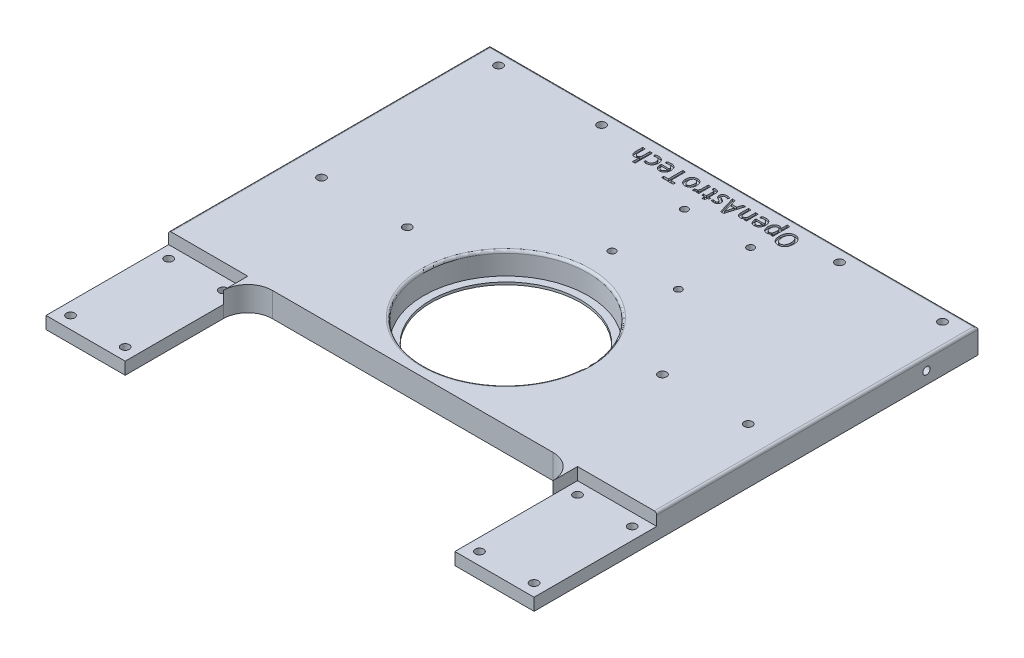
SolidWorks part; units mm, degrees
ref_plane "Ebene vorne" through (0, 0, 0) normal (0, 0, 1) x (1, 0, 0)
ref_plane "Ebene oben" through (0, 0, 0) normal (0, 1, 0) x (1, 0, 0)
ref_plane "Ebene rechts" through (0, 0, 0) normal (1, 0, 0) x (0, 0, -1)
sketch "Skizze1" plane through (0, 0, 0) normal (0, 1, 0) x (1, 0, 0)
  line L1 (-99.5, -210) -> (99.5, -210)
  line L2 (-99.5, -210) -> (-99.5, 210)
  line L3 (-99.5, 210) -> (99.5, 210)
  line L4 (99.5, -210) -> (99.5, 210)
  line L5 (-99.5, -210) -> (99.5, 210) construction
  line L6 (-99.5, 210) -> (99.5, -210) construction
  point P0 (0, 0)
  dimension "D1" = 199
  dimension "D2" = 420
extrude "Aufsatz-Linear austragen1" add sketch "Skizze1" along normal blind 10
ref_plane "Ebene1" through (0, -97.5366, 81.8429) normal (0, -0.766, 0.6428) x (1, 0, 0)
sketch "Skizze2" plane through (0, -97.5366, 81.8429) normal (0, -0.766, 0.6428) x (1, 0, 0)
  line L1 (-99.5, 167.2972) -> (99.5, 167.2972) construction
  circle A0 centre (0, 147.2972) radius 5
  dimension "D1" = 10
  dimension "D2" = 20
extrude "Schnitt-Linear austragen1" [suppressed] cut sketch "Skizze2" against normal blind 30 and the other way blind 10
sketch "Skizze3" [suppressed] plane through (0, -67.9923, 57.0523) normal (0, -0.766, 0.6428) x (1, 0, 0)
  circle A0 centre (0, 101.3345) radius 5
  dimension "D1" = 10
extrude "Aufsatz-Linear austragen2" [suppressed] add sketch "Skizze3" along normal blind 0.1
sketch "Skizze4" plane through (0, -97.5366, 81.8429) normal (0, -0.766, 0.6428) x (1, 0, 0)
  line L0 (0, 167.2972) -> (0, 159.9002) construction
  line L1 (-99.5, 167.2972) -> (99.5, 167.2972) construction
  line L2 (-25, 167.2972) -> (-25, 202.2972)
  line L3 (-25, 202.2972) -> (25, 202.2972)
  line L4 (-25, 167.2972) -> (25, 167.2972)
  line L5 (25, 167.2972) -> (25, 202.2972)
  point P10 (0, 202.2972)
  dimension "D1" = 50
  dimension "D2" = 35
extrude "Aufsatz-Linear austragen3" [suppressed] add sketch "Skizze4" against normal blind 10 separate body
sketch "Skizze5" plane through (0, 10, 0) normal (0, 1, 0) x (1, 0, 0)
  line L0 (0, 0) -> (0, -210) construction
  line L1 (-99.5, -210) -> (99.5, -210) construction
  line L2 (99.5, -210) -> (18, -210)
  line L3 (-18, -210) -> (-99.5, -56)
  line L4 (-99.5, 210) -> (-99.5, -210) construction
  line L5 (-99.5, -56) -> (-99.5, -210)
  line L6 (-99.5, -210) -> (-18, -210)
  line L7 (99.5, -56) -> (99.5, -210)
  line L8 (18, -210) -> (99.5, -56)
  line L9 (-99.5, 210) -> (-99.5, 125)
  line L10 (-99.5, 125) -> (99.5, 125)
  line L11 (99.5, -210) -> (99.5, 210) construction
  line L12 (99.5, 125) -> (99.5, 210)
  line L13 (99.5, 210) -> (-99.5, 210)
  line L14 (67.211, -56) -> (-67.211, -56)
  line L15 (-67.211, -56) -> (-2.6461, -178)
  line L16 (67.211, -56) -> (2.6461, -178)
  line L17 (-2.6461, -178) -> (2.6461, -178)
  line L18 (2.6461, -178) -> (0, -183) construction
  line L19 (-2.6461, -178) -> (0, -183) construction
  point P27 (0, -56)
  dimension "D1" = 36
  dimension "D2" = 154
  dimension "D3" = 85
  dimension "D4" = 32
  dimension "D5" = 27
extrude "Schnitt-Linear austragen2" cut sketch "Skizze5" against normal blind 10
sketch "Skizze6" plane through (0, 10, 0) normal (0, 1, 0) x (1, 0, 0)
  line L0 (0, -210) -> (0, -178) construction
  line L1 (-18, -210) -> (18, -210) construction
  line L2 (-2.6461, -178) -> (2.6461, -178) construction
  line L3 (0, -196.59) -> (-21.075, -196.59) construction
  circle A0 centre (-11, -205) radius 1.7
  circle A1 centre (-11, -188.18) radius 1.7
  circle A2 centre (11, -205) radius 1.7
  circle A3 centre (11, -188.18) radius 1.7
  dimension "D1" = 3.4
  dimension "D2" = 11
  dimension "D3" = 5
  dimension "D4" = 13.41
extrude "Schnitt-Linear austragen3" cut sketch "Skizze6" against normal through all
sketch "Skizze7" plane through (0, 0, 0) normal (0, -1, 0) x (1, 0, 0)
  line L0 (-11, 205) -> (-11, 210) construction
  line L1 (-18, 210) -> (18, 210) construction
  line L2 (-11, 205) -> (-5.1092, 205) construction
  line L3 (-11, 208.4064) -> (-8.05, 206.7032)
  line L4 (-8.05, 206.7032) -> (-8.05, 203.2968)
  line L5 (-11, 201.5936) -> (-8.05, 203.2968)
  line L6 (-11, 201.5936) -> (-13.95, 203.2968)
  line L7 (-13.95, 206.7032) -> (-13.95, 203.2968)
  line L8 (-11, 208.4064) -> (-13.95, 206.7032)
  line L9 (0, 210) -> (0, 121.6034) construction
  line L10 (11, 205) -> (11, 188.18) construction
  line L11 (11, 196.59) -> (0, 196.59) construction
  line L12 (11, 208.4064) -> (8.05, 206.7032)
  line L13 (11, 201.5936) -> (8.05, 203.2968)
  line L14 (8.05, 206.7032) -> (8.05, 203.2968)
  line L15 (11, 201.5936) -> (13.95, 203.2968)
  line L16 (13.95, 206.7032) -> (13.95, 203.2968)
  line L17 (11, 208.4064) -> (13.95, 206.7032)
  line L18 (-8.05, 186.4768) -> (-8.05, 189.8832)
  line L19 (-11, 191.5864) -> (-13.95, 189.8832)
  line L20 (-11, 191.5864) -> (-8.05, 189.8832)
  line L21 (-13.95, 186.4768) -> (-13.95, 189.8832)
  line L22 (-11, 184.7736) -> (-13.95, 186.4768)
  line L23 (-11, 184.7736) -> (-8.05, 186.4768)
  line L24 (8.05, 186.4768) -> (8.05, 189.8832)
  line L25 (11, 191.5864) -> (8.05, 189.8832)
  line L26 (11, 191.5864) -> (13.95, 189.8832)
  line L27 (13.95, 186.4768) -> (13.95, 189.8832)
  line L28 (11, 184.7736) -> (13.95, 186.4768)
  line L29 (11, 184.7736) -> (8.05, 186.4768)
  point P10 (-8.05, 205)
  dimension "D1" = 120
  dimension "D2" = 5.9
extrude "Schnitt-Linear austragen4" cut sketch "Skizze7" against normal blind 4
sketch "Skizze8" plane through (0, 10, 0) normal (0, 1, 0) x (1, 0, 0)
  line L0 (99.5, 115.41) -> (78.872, 115.41) construction
  line L1 (99.5, -56) -> (99.5, 125) construction
  line L2 (-99.5, 125) -> (99.5, 125) construction
  dimension "D1" = 9.59
ref_plane "Ebene2" through (0, 62.6966, -52.6087) normal (0, 0.766, -0.6428) x (-1, 0, 0)
sketch "Skizze9" plane through (0, 62.6966, -52.6087) normal (0, 0.766, -0.6428) x (-1, 0, 0)
  line L0 (-99.5, -81.9813) -> (-78.872, -81.9813) construction
  line L1 (-99.5, 49.3264) -> (-99.5, -89.3277) construction
  line L2 (0, -45.2589) -> (0, -16.2619) construction
  circle A0 centre (-94.5, -81.9813) radius 1.7
  circle A1 centre (94.5, -81.9813) radius 1.7
  circle A2 centre (-30, -81.9813) radius 1.7
  circle A3 centre (30, -81.9813) radius 1.7
  dimension "D1" = 3.4
  dimension "D2" = 5
  dimension "D3" = 30
extrude "Schnitt-Linear austragen5" [suppressed] cut sketch "Skizze9" against normal through all and the other way through all
ref_plane "Ebene3" through (0, 55.0361, -46.1808) normal (0, 0.766, -0.6428) x (-1, 0, 0)
sketch "Skizze10" [suppressed] plane through (0, 55.0361, -46.1808) normal (0, 0.766, -0.6428) x (-1, 0, 0)
  line L0 (-95, -81.9813) -> (-100, -81.9813) construction
  line L1 (-95, -81.9813) -> (-95, -30.0694) construction
  line L2 (-95, -78.7482) -> (-97.8, -80.3647)
  line L3 (-97.8, -80.3647) -> (-97.8, -83.5979)
  line L4 (-95, -85.2145) -> (-97.8, -83.5979)
  line L5 (-95, -85.2145) -> (-92.2, -83.5979)
  line L6 (-92.2, -80.3647) -> (-92.2, -83.5979)
  line L7 (-95, -78.7482) -> (-92.2, -80.3647)
  line L8 (0, 0) -> (0, -45.6283) construction
  line L9 (-30, -81.9813) -> (-95, -81.9813) construction
  line L10 (-62.5, -81.9813) -> (-62.5, -23.1343) construction
  line L11 (-32.8, -80.3647) -> (-32.8, -83.5979)
  line L12 (-30, -85.2145) -> (-32.8, -83.5979)
  line L13 (-30, -85.2145) -> (-27.2, -83.5979)
  line L14 (-27.2, -80.3647) -> (-27.2, -83.5979)
  line L15 (-30, -78.7482) -> (-27.2, -80.3647)
  line L16 (-30, -78.7482) -> (-32.8, -80.3647)
  line L17 (95, -78.7482) -> (92.2, -80.3647)
  line L18 (92.2, -80.3647) -> (92.2, -83.5979)
  line L19 (95, -85.2145) -> (92.2, -83.5979)
  line L20 (95, -85.2145) -> (97.8, -83.5979)
  line L21 (97.8, -80.3647) -> (97.8, -83.5979)
  line L22 (95, -78.7482) -> (97.8, -80.3647)
  line L23 (30, -78.7482) -> (32.8, -80.3647)
  line L24 (30, -78.7482) -> (27.2, -80.3647)
  line L25 (27.2, -80.3647) -> (27.2, -83.5979)
  line L26 (30, -85.2145) -> (27.2, -83.5979)
  line L27 (30, -85.2145) -> (32.8, -83.5979)
  line L28 (32.8, -80.3647) -> (32.8, -83.5979)
  point P9 (-97.8, -81.9813)
  point P31 (97.8, -81.9813)
  dimension "D1" = 120
  dimension "D2" = 5.6
extrude "Schnitt-Linear austragen6" [suppressed] cut sketch "Skizze10" against normal blind 10 and the other way blind 5
sketch "Skizze13" plane through (0, 10, 0) normal (0, 1, 0) x (1, 0, 0)
  line L0 (67.211, -56) -> (99.5, -56) construction
  line L1 (67.211, -56) -> (92.4353, -69.3492) construction
  line L2 (99.5, -56) -> (18, -210) construction
  line L3 (0, 0) -> (0, -38.1435) construction
  line L4 (2.6461, -178) -> (67.211, -56) construction
  line L5 (79.8232, -62.6746) -> (103.8351, -17.3024) construction
  line L6 (99.5, -56) -> (99.5, 125) construction
  line L7 (83.3555, -56) -> (83.3555, -1) construction
  line L8 (93.5, -58.8065) -> (101.0692, -44.504) construction
  line L9 (83.1285, -86.935) -> (57.9043, -73.5858) construction
  line L10 (71.7911, -80.935) -> (86.3039, -80.935) construction
  circle A0 centre (93.5, -58.8065) radius 1.7
  circle A1 centre (72.5142, -58.8065) radius 1.7
  circle A2 centre (81.7891, -80.935) radius 1.7
  circle A3 centre (-81.7891, -80.935) radius 1.7
  circle A4 centre (-93.5, -58.8065) radius 1.7
  circle A5 centre (-72.5142, -58.8065) radius 1.7
  dimension "D1" = 6
  dimension "D5" = 35
  dimension "D3" = 3.4
  dimension "D6" = 3.4
  dimension "D2" = 6
  dimension "D4" = 6
extrude "Schnitt-Linear austragen7" [suppressed] cut sketch "Skizze13" against normal through all
sketch "Skizze14" plane through (100.8819, 0, 53.3888) normal (0.8839, 0, 0.4678) x (0.4678, 0, -0.8839)
  line L0 (-37.9543, 5) -> (-37.9543, 10)
  line L5 (-2.9543, 0) -> (-2.9543, 10) construction
  line L6 (-37.9543, 5) -> (-2.9543, 5)
  line L7 (-2.9543, 10) -> (-177.1905, 10) construction
  line L8 (-37.9543, 10) -> (-2.9543, 10)
  line L9 (-2.9543, 10) -> (-2.9543, 5)
  dimension "D1" = 35
extrude "Schnitt-Linear austragen8" [suppressed] cut sketch "Skizze14" against normal up to surface (28.9525 mm away)
mirror "Spiegeln1" [suppressed] about plane through (0, 0, 0) normal (1, 0, 0)
sketch "Skizze15" [suppressed] plane through (95, 0, 0) normal (1, 0, 0) x (0, 0, -1)
  line L0 (4, 10) -> (4, 0)
  line L1 (4, 0) -> (65, 0)
  line L2 (65, 0) -> (65, 10)
  line L3 (65, 10) -> (4, 10)
extrude "Schnitt-Linear austragen9" [suppressed] cut sketch "Skizze15" against normal through all
sketch "Skizze16" plane through (0, 0, 0) normal (0, -1, 0) x (1, 0, 0)
  line L0 (0, 210) -> (0, 178) construction
  line L1 (-18, 210) -> (18, 210) construction
  line L2 (-2.6461, 178) -> (2.6461, 178) construction
  line L3 (11, 196.59) -> (0, 196.59) construction
  line L4 (11, 205) -> (11, 188.18) construction
  line L6 (-17.5, 193.09) -> (17.5, 193.09)
  line L7 (-17.5, 193.09) -> (-17.5, 200.09)
  line L8 (-17.5, 200.09) -> (17.5, 200.09)
  line L9 (17.5, 193.09) -> (17.5, 200.09)
  line L10 (-17.5, 193.09) -> (17.5, 200.09) construction
  line L11 (-17.5, 200.09) -> (17.5, 193.09) construction
  dimension "D1" = 7
  dimension "D2" = 35
extrude "Schnitt-Linear austragen10" cut sketch "Skizze16" against normal blind 5
sketch "Skizze17" plane through (17.5, 0, 0) normal (-1, 0, 0) x (0, 0, 1)
  line L0 (196.59, 0) -> (196.59, 11.1261) construction
  line L1 (193.09, 0) -> (200.09, 0) construction
  line L2 (193.09, 5) -> (196.59, 8.5)
  line L3 (196.59, 8.5) -> (200.09, 5)
  line L4 (200.09, 5) -> (193.09, 5)
  dimension "D1" = 90
extrude "Schnitt-Linear austragen11" cut sketch "Skizze17" along normal up to surface (35 mm away) up to face at (-17.5, 2.5, 196.59)
sketch "Skizze18" [suppressed] plane through (0, 10, 0) normal (0, 1, 0) x (1, 0, 0)
  line L0 (0, -210) -> (0, 0) construction
  line L1 (-18, -210) -> (18, -210) construction
  line L2 (62.5765, -72.2325) -> (35.4483, -67.5372)
  line L3 (15.3378, -155.8503) -> (-22.1774, -134.6566)
  line L4 (2.8247, -178) -> (62.5765, -72.2325) construction
  line L5 (-15.3378, -155.8503) -> (22.1774, -134.6566)
  line L6 (58.6594, -79.166) -> (40.7308, -76.063)
  line L7 (0, -147.1854) -> (19.5429, -147.1854) construction
  line L8 (0, -95.4) -> (31.4297, -95.4) construction
  line L9 (11.6488, -162.3803) -> (0, -155.7995)
  line L10 (-71.7468, -56) -> (-2.8247, -178) construction
  line L11 (0, -95.4) -> (-37.5153, -116.5937) construction
  line L12 (-37.5153, -116.5937) -> (-39.2566, -117.5774) construction
  line L13 (-11.6488, -162.3803) -> (0, -155.7995)
  line L14 (-58.6594, -79.166) -> (-40.7308, -76.063)
  line L15 (-62.5765, -72.2325) -> (-35.4483, -67.5372)
  circle A0 centre (0, -95.4) radius 33.5
  arc A1 (7.4594, -151.3994) -> (7.4594, -142.9713) centre (9.84, -147.1854) cw
  arc A2 (-7.4594, -151.3994) -> (-7.4594, -142.9713) centre (-9.84, -147.1854) ccw
  circle A3 centre (0, -95.4) radius 45.0879
  point P17 (0, -147.1854)
  point P36 (5, -147.1854)
  point P40 (-5, -147.1854)
  line M16 (62.5765, -72.2325) -> (2.8247, -178)
  line M18 (-2.8247, -178) -> (-71.7468, -56)
  dimension "D2" = 67
  dimension "D5" = 2
  dimension "D4" = 10
  dimension "D1" = 114.6
  dimension "D3" = 7.5
  dimension "D6" = 7.5
extrude "Aufsatz-Linear austragen4" [suppressed] add sketch "Skizze18" against normal blind 10 contours A3 L15 L14 M18 | A3 A0 M16 M18 | A3 L6 L2 M16 | A2 L5 L3 | A3 L3 L5 | L3 A1 L5 | L13 L9 L3 L5 M18 M16
sketch "Skizze19" [suppressed] plane through (0, 0, 0) normal (0, -1, 0) x (1, 0, 0)
  circle A0 centre (0, 35.4) radius 31.5
  circle A1 centre (0, 35.4) radius 33.5
  circle A2 centre (0, 35.4) radius 33.5 construction
  dimension "D1" = 63
extrude "Aufsatz-Linear austragen5" [suppressed] add sketch "Skizze19" against normal blind 1
sketch "Skizze20" plane through (0, 10, 0) normal (0, 1, 0) x (1, 0, 0)
  line L0 (99.5, 119.52) -> (55.4083, 119.52) construction
  line L1 (99.5, -56) -> (99.5, 125) construction
  line L2 (-99.5, 125) -> (99.5, 125) construction
  line L3 (0, 125) -> (0, 96.9732) construction
  line L4 (105, 43.82) -> (35.5869, 43.82) construction
  circle A0 centre (90.5, 119.52) radius 1.7
  circle A1 centre (48.5, 119.52) radius 1.7
  circle A2 centre (-48.5, 119.52) radius 1.7
  circle A3 centre (-90.5, 119.52) radius 1.7
  circle A4 centre (87, 43.82) radius 1.7
  circle A5 centre (52, 43.82) radius 1.7
  circle A6 centre (-87, 43.82) radius 1.7
  circle A7 centre (-52, 43.82) radius 1.7
  dimension "D1" = 3.4
  dimension "D2" = 5.48
  dimension "D3" = 9
  dimension "D4" = 42
  dimension "D5" = 75.7
  dimension "D6" = 12.5
  dimension "D7" = 35
extrude "Schnitt-Linear austragen12" cut sketch "Skizze20" against normal through all
sketch "Skizze21" plane through (0, 10, 0) normal (0, 1, 0) x (1, 0, 0)
  line L0 (-67.211, -56) -> (-67.211, -6)
  line L1 (-67.211, -6) -> (67.211, -6)
  line L2 (67.211, -6) -> (67.211, -56)
  line L3 (67.211, -56) -> (-67.211, -56) construction
  line L4 (-67.211, -56) -> (67.211, -56)
  dimension "D1" = 50
extrude "Schnitt-Linear austragen13" cut sketch "Skizze21" against normal through all
sketch "Skizze22" plane through (0, 10, 0) normal (0, 1, 0) x (1, 0, 0)
  line L0 (-67.211, -56) -> (-2.6461, -178)
  arc A0 (-67.211, -56) -> (-2.6461, -178) centre (60.0769, -66.7211) ccw
  line M19 (-2.6461, -178) -> (-67.211, -56)
extrude "Schnitt-Linear austragen14" cut sketch "Skizze22" against normal through all contours M19 region at (-42.1385, 10, 120.8156)
sketch "Skizze23" plane through (0, 10, 0) normal (0, 1, 0) x (1, 0, 0)
  line L0 (-18, -210) -> (-99.5, -56) construction
  line L1 (-99.5, -56) -> (-18, -210)
  arc A0 (-18, -210) -> (-99.5, -56) centre (114.4449, -41.3416) cw
  arc A2 (-67.211, -56) -> (-2.6461, -178) centre (60.0769, -66.7211) ccw construction
  dimension "D1" = 60
extrude "Aufsatz-Linear austragen6" add sketch "Skizze23" against normal blind 10
mirror "Spiegeln2" about plane through (0, 0, 0) normal (1, 0, 0) of "Aufsatz-Linear austragen6", "Schnitt-Linear austragen14"
sketch "Skizze25" plane through (0, 10, 0) normal (0, 1, 0) x (1, 0, 0)
  line L0 (-99.5, -56) -> (-67.211, -56) construction
  line L1 (-99.5, -6) -> (-99.5, -56) construction
  line L2 (-99.5, -6) -> (-67.211, -6) construction
  line L3 (-67.211, -6) -> (-67.211, -56) construction
  line L4 (-83.3555, -6) -> (-83.3555, -56) construction
  line L5 (-99.5, -31) -> (-67.211, -31) construction
  line L6 (-99.5, 125) -> (-99.5, -56) construction
  circle A0 centre (-94.5, -11) radius 1.7
  circle A1 centre (-72.211, -11) radius 1.7
  circle A2 centre (-72.211, -51) radius 1.7
  circle A3 centre (-94.5, -51) radius 1.7
  dimension "D2" = 3.4
  dimension "D1" = 50
  dimension "D3" = 5
  dimension "D4" = 5
extrude "Schnitt-Linear austragen15" cut sketch "Skizze25" against normal through all
sketch "Skizze26" plane through (-99.5, 0, 0) normal (-1, 0, 0) x (0, 0, 1)
  line L0 (6, 5) -> (6, 13.1015)
  line L1 (56, 0) -> (56, 10) construction
  line L2 (56, 5) -> (6, 5)
  line L4 (-125, 0) -> (56, 0) construction
  line L5 (56, 5) -> (56, 0)
  line L6 (6, 13.1015) -> (200.6846, 82.5463)
  line L7 (200.6846, 82.5463) -> (242.9972, -41.0376)
  line L8 (242.9972, -41.0376) -> (91.2415, -60.2848)
  line L9 (91.2415, -60.2848) -> (56, 0)
  dimension "D1" = 50
mirror "Spiegeln3" about plane through (0, 0, 0) normal (1, 0, 0) of "Schnitt-Linear austragen15"
extrude "Schnitt-Linear austragen16" cut sketch "Skizze26" against normal through all
sketch "Skizze27" plane through (0, 10, 0) normal (0, 1, 0) x (1, 0, 0)
  line L0 (0, -6) -> (0, 125) construction
  line L1 (99.5, -6) -> (-99.5, -6) construction
  line L2 (-99.5, 125) -> (99.5, 125) construction
  line L3 (99.5, -6) -> (-99.5, -6) construction
  circle A0 centre (0, 32) radius 33.5
  dimension "D1" = 67
  dimension "D2" = 38
extrude "Schnitt-Linear austragen17" cut sketch "Skizze27" against normal through all
sketch "Skizze28" plane through (0, 0, 0) normal (0, -1, 0) x (1, 0, 0)
  circle A0 centre (0, -32) radius 30.5
  circle A1 centre (0, -32) radius 33.5 construction
  circle A2 centre (0, -32) radius 36.0063
  dimension "D1" = 3
extrude "Aufsatz-Linear austragen7" add sketch "Skizze28" against normal blind 1
sketch "Skizze29" plane through (-99.5, 0, 0) normal (-1, 0, 0) x (0, 0, 1)
  line L0 (-125, 5) -> (-93.4233, 5) construction
  line L1 (-125, 0) -> (-125, 10) construction
  circle A0 centre (-104, 5) radius 1.5
  dimension "D1" = 3
  dimension "D2" = 21
extrude "Schnitt-Linear austragen18" cut sketch "Skizze29" against normal blind 10
sketch "Skizze30" plane through (0, 0, -125) normal (0, 0, -1) x (-1, 0, 0)
  line L0 (99.5, 5) -> (60.2539, 5) construction
  line L1 (99.5, 0) -> (99.5, 10) construction
  circle A0 centre (94.5, 5) radius 1.5
  circle A1 centre (78.5, 5) radius 1.5
  dimension "D1" = 3
  dimension "D2" = 5
  dimension "D3" = 21
extrude "Schnitt-Linear austragen19" cut sketch "Skizze30" against normal blind 10
mirror "Spiegeln4" about plane through (0, 0, 0) normal (1, 0, 0) of "Schnitt-Linear austragen18", "Schnitt-Linear austragen19"
sketch "Skizze31" plane through (0, 0, 0) normal (0, -1, 0) x (1, 0, 0)
  line L0 (0, -125) -> (0, -73.0202) construction
  line L1 (-99.5, -125) -> (99.5, -125) construction
  circle A0 centre (-90.5, -119.52) radius 2.95
  circle A1 centre (-48.5, -119.52) radius 2.95
  circle A2 centre (-87, -43.82) radius 2.95
  circle A3 centre (-52, -43.82) radius 2.95
  circle A4 centre (52, -43.82) radius 2.95
  circle A5 centre (87, -43.82) radius 2.95
  circle A6 centre (48.5, -119.52) radius 2.95
  circle A7 centre (90.5, -119.52) radius 2.95
  dimension "D1" = 5.9
extrude "Schnitt-Linear austragen20" cut sketch "Skizze31" against normal blind 3.5
move or copy body "Körper-Verschieben/Kopieren1" [suppressed] bodies to move or copy 132 copy no rotation origin (0, 5, -34.5) rotation axis (1, 0, 0) rotation angle 90
sketch "Skizze32" plane through (0, 10, 0) normal (0, 1, 0) x (1, 0, 0)
  line L1 (25.1613, 106.641) -> (-1.8387, 106.641)
  line L2 (25.1613, 106.641) -> (25.1613, 77.141)
  line L3 (25.1613, 77.141) -> (-1.8387, 77.141)
  line L4 (-1.8387, 106.641) -> (-1.8387, 77.141)
  line L5 (25.1613, 106.641) -> (-1.8387, 77.141) construction
  line L6 (25.1613, 77.141) -> (-1.8387, 106.641) construction
  circle A0 centre (25.1613, 77.141) radius 1.45
  circle A1 centre (-1.8387, 77.141) radius 1.45
  circle A2 centre (-1.8387, 106.641) radius 1.45
  circle A3 centre (25.1613, 106.641) radius 1.45
  point P0 (11.6613, 91.891)
  dimension "D3" = 2.9
  dimension "D1" = 29.5
  dimension "D2" = 27
extrude "Schnitt-Linear austragen21" cut sketch "Skizze32" against normal through all contours L3 A0 L2 | L2 A0 L3 | L4 A1 L3 | L3 A1 L4 | L1 A2 L4 | L4 A2 L1 | L2 A3 L1 | L1 A3 L2 region at (-1.2233, 10, -106.0256) region at (-2.0439, 10, -106.8462) region at (25.3664, 10, -106.8462) region at (24.5459, 10, -106.0256) region at (-1.2233, 10, -77.7564) region at (-2.0439, 10, -76.9359) region at (25.3664, 10, -76.9359) region at (24.5459, 10, -77.7564)
fillet "Verrundung1" radius 10 2 edges at (-67.211, 2.5, 6) (67.211, 2.5, 6)
sketch "Skizze33" plane through (0, 5, 0) normal (0, 1, 0) x (1, 0, 0)
  line L0 (-67.211, -16) -> (-67.211, -6)
  line L1 (-57.211, -6) -> (-99.5, -6) construction
  line L2 (-67.211, -6) -> (-57.211, -6)
  line L3 (99.5, -6) -> (-99.5, -6) construction
  line L4 (0, -6) -> (0, -39.688) construction
  line L5 (67.211, -6) -> (57.211, -6)
  line L6 (67.211, -16) -> (67.211, -6)
  arc A0 (-57.211, -6) -> (-67.211, -16) centre (-57.211, -16) ccw construction
  arc A1 (-67.211, -16) -> (-57.211, -6) centre (-57.211, -16) cw
  arc A2 (67.211, -16) -> (57.211, -6) centre (57.211, -16) ccw
extrude "Aufsatz-Linear austragen8" add sketch "Skizze33" along normal up to surface (5 mm away) up to face at (-1.8387, 10, -75.691)
fillet "Verrundung2" radius 1 4 edges at (0, 10, 1.5) (99.5, 10, -59.5) (0, 10, -125) (-99.5, 10, -59.5)
sketch "Skizze34" plane through (0, 10, 0) normal (0, 1, 0) x (1, 0, 0)
  line L0 (50.1242, 120.022) -> (-50.1242, 120.022) construction
  circle A0 centre (-48.5, 119.52) radius 1.7 construction
  circle A1 centre (48.5, 119.52) radius 1.7 construction
  text T0 "OpenAstroTech" font "@Adobe Heiti Std R" height in points 22
extrude "Schnitt-Linear austragen22" cut sketch "Skizze34" against normal blind 0.8
sketch "Skizze35" plane through (0, 0, 0) normal (0, 1, 0) x (1, 0, 0)
  line L6 (-100, -66.8798) -> (100, -66.8798)
  line L7 (-100, -66.8798) -> (-100, 133.1202)
  line L8 (-100, 133.1202) -> (100, 133.1202)
  line L9 (100, -66.8798) -> (100, 133.1202)
  line L10 (-100, -66.8798) -> (100, 133.1202) construction
  line L11 (-100, 133.1202) -> (100, -66.8798) construction
  point P0 (0, 33.1202)
  point P2 (0, 33.1202)
  dimension "D1" = 200
